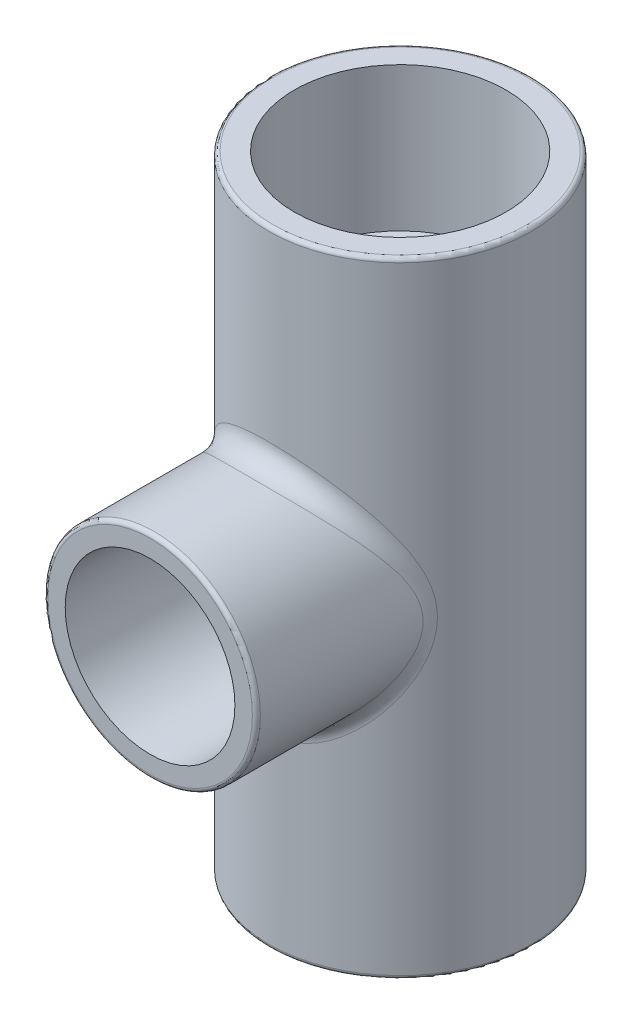
SolidWorks part; units mm, degrees
ref_plane "Front Plane" through (0, 0, 0) normal (0, 0, 1) x (1, 0, 0)
ref_plane "Top Plane" through (0, 0, 0) normal (0, 1, 0) x (1, 0, 0)
ref_plane "Right Plane" through (0, 0, 0) normal (1, 0, 0) x (0, 0, -1)
sketch "Sketch1" plane through (0, 0, 0) normal (0, 1, 0) x (1, 0, 0)
  circle A0 centre (0, 0) radius 656.5
  circle A1 centre (0, 0) radius 412
  dimension "D1" = 824
  dimension "D2" = 1313
extrude "Boss-Extrude1" add sketch "Sketch1" along normal blind 3125
sketch "Sketch2" plane through (0, 3125, 0) normal (0, 1, 0) x (1, 0, 0)
  circle A0 centre (0, 0) radius 529
  dimension "D1" = 1058
extrude "Cut-Extrude1" cut sketch "Sketch2" against normal blind 720
sketch "Sketch3" plane through (0, 0, 0) normal (0, -1, 0) x (1, 0, 0)
  circle A0 centre (0, 0) radius 529
  dimension "D1" = 1058
extrude "Cut-Extrude2" cut sketch "Sketch3" against normal blind 720
sketch "Sketch4" plane through (0, 0, 0) normal (0, 0, 1) x (1, 0, 0)
  line L0 (0, 3125) -> (0, 0) construction
  line L1 (656.5, 3125) -> (-656.5, 3125) construction
  circle A0 centre (0, 1562.5) radius 531.5
  circle A1 centre (0, 1562.5) radius 311
  dimension "D1" = 1063
  dimension "D2" = 622
extrude "Boss-Extrude3" add sketch "Sketch4" along normal blind 1250
sketch "Sketch6" plane through (0, 0, 1250) normal (0, 0, 1) x (1, 0, 0)
  line L0 (0, 2094) -> (0, 1031) construction
  circle A0 centre (0, 1562.5) radius 531.5 construction
  circle A1 centre (0, 1562.5) radius 531.5 construction
  circle A2 centre (0, 1562.5) radius 424
  dimension "D1" = 848
extrude "Cut-Extrude3" cut sketch "Sketch6" against normal blind 690
sketch "Sketch7" plane through (0, 0, 560) normal (0, 0, 1) x (1, 0, 0)
  line L0 (0, 1986.5) -> (0, 1138.5) construction
  circle A0 centre (0, 1562.5) radius 424 construction
  circle A1 centre (0, 1562.5) radius 424 construction
  circle A2 centre (0, 1562.5) radius 311
  dimension "D1" = 622
extrude "Cut-Extrude4" cut sketch "Sketch7" against normal blind 690
sketch "Sketch8" plane through (0, 2405, 0) normal (0, 1, 0) x (1, 0, 0)
  circle A0 centre (0, 0) radius 412
  dimension "D1" = 824
extrude "Cut-Extrude5" cut sketch "Sketch8" against normal blind 4871
fillet "Fillet1" radius 100 1 edges at (524.4649, 1648.6906, 394.8782)
fillet "Fillet2" radius 20 3 edges at (531.5, 1562.5, 1250) (0, 0, 656.5) (0, 3125, 656.5)
